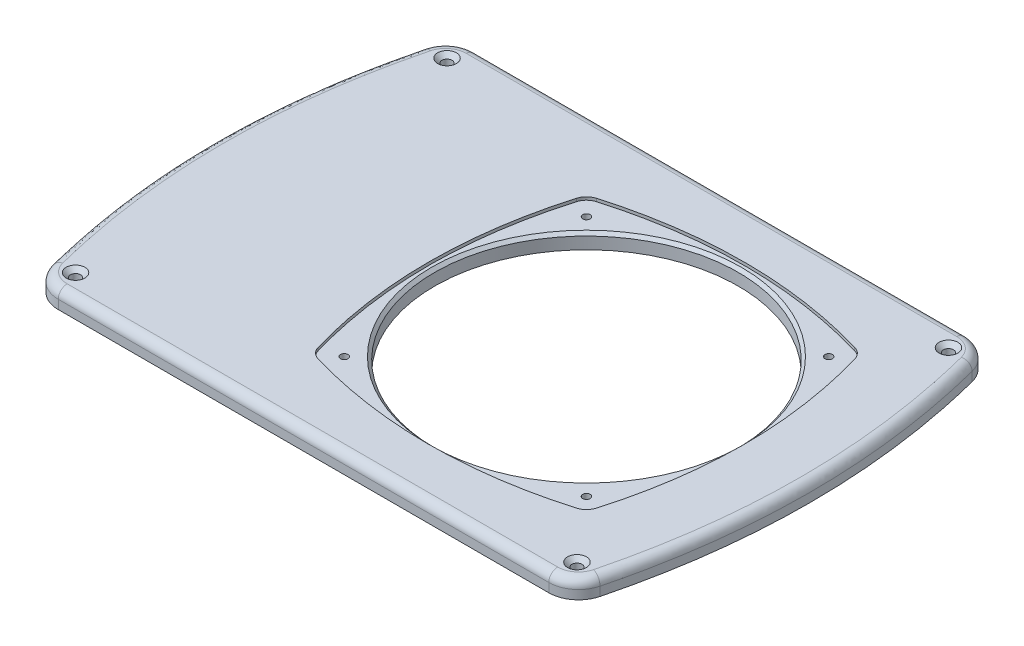
SolidWorks part; units mm, degrees
ref_plane "Front Plane" through (0, 0, 0) normal (0, 0, 1) x (1, 0, 0)
ref_plane "Top Plane" through (0, 0, 0) normal (0, 1, 0) x (1, 0, 0)
ref_plane "Right Plane" through (0, 0, 0) normal (1, 0, 0) x (0, 0, -1)
sketch "Sketch1" plane through (0, 0, 0) normal (0, 1, 0) x (1, 0, 0)
  line L0 (-100, 80) -> (-100, -80) construction
  line L1 (-90, 70) -> (90, 70)
  line L2 (-90, 70) -> (-90, -70) construction
  line L3 (-90, -70) -> (90, -70)
  line L4 (90, 70) -> (90, -70) construction
  line L5 (-90, 70) -> (90, -70) construction
  line L6 (-90, -70) -> (90, 70) construction
  line L8 (100, 80) -> (100, -80) construction
  line L10 (-100, -80) -> (100, -80) construction
  line L11 (-100, 80) -> (100, 80) construction
  spline S0 degree 2 poles (-90, 70) (-110, 0) (-90, -70) knots 0 0 0 1 1 1
  spline S1 degree 2 poles (90, 70) (110, 0) (90, -70) knots 0 0 0 1 1 1
  point P0 (0, 0)
  dimension "D1" = 180
  dimension "D2" = 140
  dimension "D3" = 10
extrude "Boss-Extrude1" add sketch "Sketch1" along normal blind 6
fillet "Fillet1" radius 10 4 edges at (-90, 3, -70) (90, 3, -70) (90, 3, 70) (-90, 3, 70)
fillet "Fillet2" radius 3 8 edges at (-88.4812, 6, -67.8964) (0, 6, -70) (88.4812, 6, -67.8964) (88.4812, 6, 67.8964) (0, 6, 70) (-88.4812, 6, 67.8964)
sketch "Sketch2" plane through (0, 6, 0) normal (0, 1, 0) x (1, 0, 0)
  line L0 (-82.3456, 60) -> (-88.4812, 67.8964) construction
  line L1 (82.3456, 60) -> (88.4812, 67.8964) construction
  line L2 (82.3456, -60) -> (88.4812, -67.8964) construction
  line L3 (-82.3456, -60) -> (-88.4812, -67.8964) construction
  circle A0 centre (25, 0) radius 51
  circle A1 centre (25, 0) radius 53 construction
  circle A2 centre (25, 0) radius 57.5 construction
  circle A3 centre (25, 0) radius 64.25 construction
  circle A4 centre (25, 0) radius 65 construction
  circle A5 centre (25, 0) radius 67 construction
  arc A6 (-82.3456, 70) -> (-92.0355, 62.4708) centre (-82.3456, 60) ccw construction
  arc A7 (92.0355, 62.4708) -> (82.3456, 70) centre (82.3456, 60) ccw construction
  arc A8 (82.3456, -70) -> (92.0355, -62.4708) centre (82.3456, -60) ccw construction
  arc A9 (-92.0355, -62.4708) -> (-82.3456, -70) centre (-82.3456, -60) ccw construction
  spline S0 degree 2 poles (-20.9619, 45.9619) (-35.0381, 0) (-20.9619, -45.9619) knots 0 0 0 1 1 1
  spline S1 degree 2 poles (-20.9619, 45.9619) (25, 60.0381) (70.9619, 45.9619) knots 0 0 0 1 1 1
  spline S2 degree 2 poles (70.9619, 45.9619) (85.0381, 0) (70.9619, -45.9619) knots 0 0 0 1 1 1
  spline S3 degree 2 poles (70.9619, -45.9619) (25, -60.0381) (-20.9619, -45.9619) knots 0 0 0 1 1 1
  point P8 (78, 0)
  point P9 (25, -53)
  point P10 (-28, 0)
  point P11 (25, 53)
  point P12 (70.9619, 45.9619)
  point P13 (65.6586, 40.6586)
  point P16 (70.9619, -45.9619)
  point P17 (-20.9619, -45.9619)
  point P18 (-20.9619, 45.9619)
  point P19 (25, 0)
  point P21 (-15.6586, 40.6586)
  point P22 (-15.6586, -40.6586)
  point P23 (65.6586, -40.6586)
  point P24 (25, 0)
  point P36 (-84.1863, 62.3689)
  point P37 (84.1863, 62.3689)
  point P50 (84.1863, -62.3689)
  point P57 (-84.1863, -62.3689)
  dimension "D1" = 25
  dimension "D2" = 102
  dimension "D3" = 106
  dimension "D4" = 115
  dimension "D5" = 128.5
  dimension "D6" = 130
  dimension "D7" = 134
  dimension "D8" = 45
  dimension "D10" = 45
  dimension "D11" = 65
  dimension "D12" = 45
  dimension "D14" = 45
  dimension "D15" = 57.5
  dimension "D16" = 7
  dimension "D17" = 7
  dimension "D18" = 7
  dimension "D19" = 7
  dimension "D9" = 4
  dimension "D13" = 4
extrude "Cut-Extrude1" cut sketch "Sketch2" against normal up to next contours A0
hole_wizard "M3x0.5 Tapped Hole1" positions "3DSketch1" profile "Sketch3" tap size "M3x0.5" standard "ANSI Metric" end condition up to next
sketch3d "3DSketch1"
  point P0 (65.6586, 6, -40.6586)
  point P3 (65.6586, 6, 40.6586)
  point P6 (-15.6586, 6, 40.6586)
  point P9 (-15.6586, 6, -40.6586)
sketch "Sketch3" plane through (65.6586, 6, -40.6586) normal (1, 0, 0) x (0, 0, 1)
  line L0 (0, 0) -> (0, 6)
  line L1 (0, 6) -> (1.25, 6)
  line L2 (1.25, 6) -> (1.25, 0)
  line L5 (1.25, 0) -> (0, 0)
  line L11 (0, -6.35) -> (0, 107.95) construction
  dimension "Thread Major Dia." = 2.5
  dimension "Thru Tap Drill Depth" = 6
extrude "Cut-Extrude2" cut sketch "Sketch2<3>" against normal blind 1
sketch "Sketch2<3>" plane through (0, 6, 0) normal (0, 1, 0) x (1, 0, 0) same geometry as "Sketch2"
fillet "Fillet3" radius 5 4 edges at (-20.9619, 5.5, 45.9619) (70.9619, 5.5, 45.9619) (70.9619, 5.5, -45.9619) (-20.9619, 5.5, -45.9619)
hole_wizard "CSK for M3 Flat Head Machine Screw6" positions "Sketch14" profile "Sketch15" countersink size "M3" standard "ANSI Metric" end condition up to next
sketch "Sketch14" plane through (0, 6, 0) normal (0, 1, 0) x (1, 0, 0)
  point P0 (-84.1863, 62.3689)
  point P3 (84.1863, 62.3689)
  point P6 (84.1863, -62.3689)
  point P9 (-84.1863, -62.3689)
sketch "Sketch15" plane through (-84.1863, 6, -62.3689) normal (1, 0, 0) x (0, 0, 1)
  line L0 (0, 0) -> (0, 6)
  line L1 (0, 6) -> (1.7, 6)
  line L2 (1.7, 6) -> (1.7, 1.45)
  line L3 (1.7, 1.45) -> (3.15, 0)
  line L5 (3.15, 0) -> (0, 0)
  line L6 (-1.7, 1.45) -> (-3.15, 0) construction
  line L11 (0, -6.35) -> (0, 107.95) construction
  dimension "Thru Hole Dia." = 3.4
  dimension "Thru Hole Depth" = 6
  dimension "Near C'Sink Dia." = 6.3
  dimension "Near C'Sink Angle" = 90
chamfer "Chamfer1" distance 1 angle 45 1 edges at (25, 5, 51)
